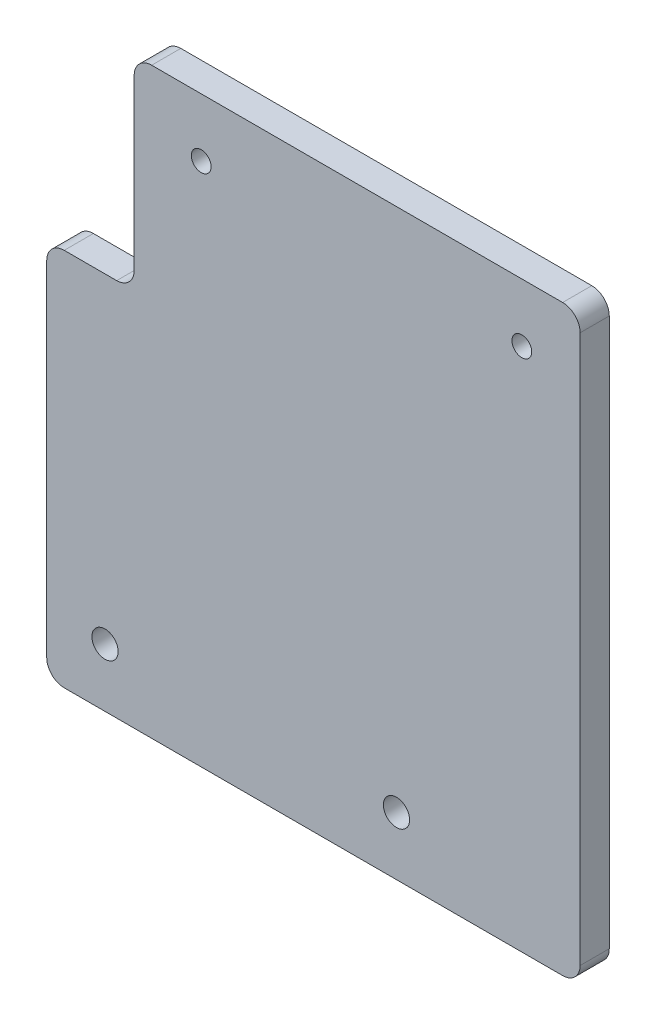
SolidWorks part; units mm, degrees
material "ABS"
ref_plane "Front Plane" through (0, 0, 0) normal (0, 0, 1) x (1, 0, 0)
ref_plane "Top Plane" through (0, 0, 0) normal (0, 1, 0) x (1, 0, 0)
ref_plane "Right Plane" through (0, 0, 0) normal (1, 0, 0) x (0, 0, -1)
sketch "Sketch1" plane through (0, 0, 0) normal (0, 0, 1) x (1, 0, 0)
  line L0 (25, 0) -> (-25, 0) construction
  line L1 (-8.5, 0) -> (-8.5, 80) construction
  line L2 (-8.5, 80) -> (46.5, 80) construction
  line L4 (56.5, -10) -> (-35, -10)
  line L5 (56.5, -10) -> (56.5, 90)
  line L6 (56.5, 90) -> (-35, 90)
  line L7 (-35, -10) -> (-35, 90)
  line L8 (56.5, -10) -> (-35, 90) construction
  line L9 (56.5, 90) -> (-35, -10) construction
  point P4 (0, 0)
  point P7 (10.75, 40)
  dimension "D1" = 80
  dimension "D2" = 16.5
  dimension "D3" = 55
  dimension "D4" = 50
  dimension "D5" = 10
  dimension "D6" = 10
  dimension "D7" = 10
  dimension "D8" = 10
extrude "Boss-Extrude1" add sketch "Sketch1" along normal blind 5
hole_wizard "M4 Clearance Hole1" positions "Sketch2" profile "Sketch3" hole size "M4" standard "ANSI Metric" end condition through all
sketch "Sketch2" plane through (0, 0, 5) normal (0, 0, 1) x (1, 0, 0)
  point P0 (-25, 0)
  point P3 (25, 0)
sketch "Sketch3" plane through (-25, 0, 5) normal (1, 0, 0) x (0, -1, 0)
  line L0 (0, 0) -> (0, 5)
  line L1 (0, 5) -> (2.25, 5)
  line L2 (2.25, 5) -> (2.25, 0)
  line L5 (2.25, 0) -> (0, 0)
  line L11 (0, -6.35) -> (0, 107.95) construction
  dimension "Thru Hole Dia." = 4.5
  dimension "Thru Hole Depth" = 5
hole_wizard "M3 Clearance Hole1" positions "Sketch4" profile "Sketch5" hole size "M3" standard "ANSI Metric" end condition through all
sketch "Sketch4" plane through (0, 0, 5) normal (0, 0, 1) x (1, 0, 0)
  point P0 (-8.5, 80)
  point P3 (46.5, 80)
sketch "Sketch5" plane through (-8.5, 80, 5) normal (1, 0, 0) x (0, -1, 0)
  line L0 (0, 0) -> (0, 5)
  line L1 (0, 5) -> (1.7, 5)
  line L2 (1.7, 5) -> (1.7, 0)
  line L5 (1.7, 0) -> (0, 0)
  line L11 (0, -6.35) -> (0, 107.95) construction
  dimension "Thru Hole Dia." = 3.4
  dimension "Thru Hole Depth" = 5
sketch "Sketch6" plane through (0, 0, 5) normal (0, 0, 1) x (1, 0, 0)
  line L0 (56.5, 90) -> (-35, 90) construction
  line L1 (-20, 90) -> (-35, 90)
  line L2 (-20, 90) -> (-20, 55)
  line L3 (-20, 55) -> (-35, 55)
  line L4 (-35, 90) -> (-35, 55)
  line L5 (-35, 90) -> (-35, -10) construction
  dimension "D1" = 35
  dimension "D2" = 15
extrude "Cut-Extrude1" cut sketch "Sketch6" against normal through all
fillet "Fillet1" radius 3 6 edges at (56.5, 90, 2.5) (56.5, -10, 2.5) (-35, -10, 2.5) (-20, 90, 2.5) (-20, 55, 2.5) (-35, 55, 2.5)
